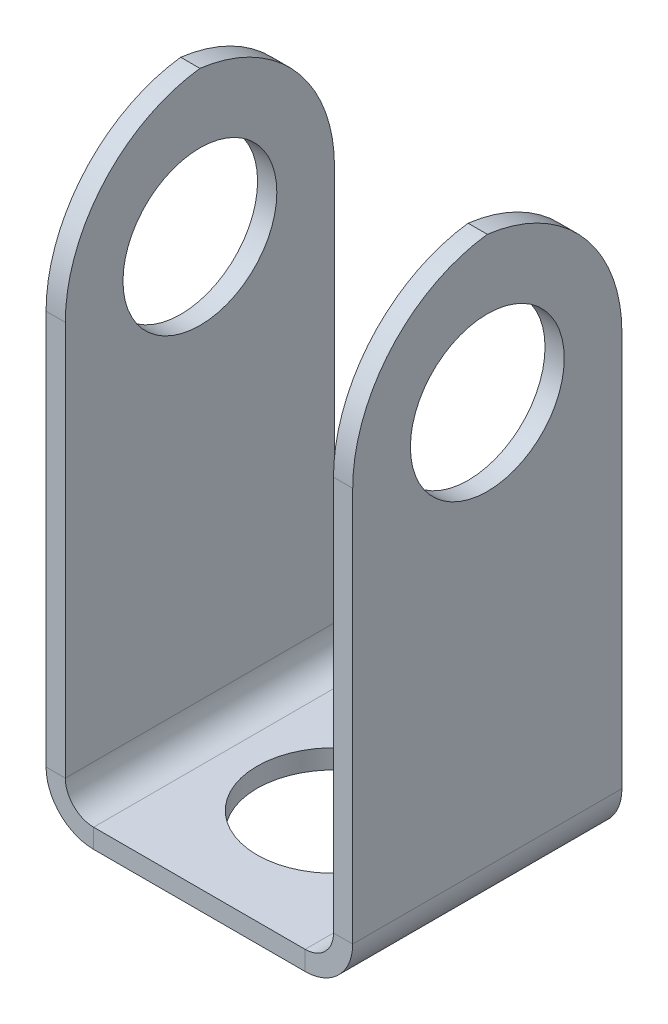
SolidWorks part; units mm, degrees
note: The reader was unsure of these and kept them because the rebuilt part matched: flange length of "Edge-Flange1", "Edge-Flange2".
ref_plane "Front Plane" through (0, 0, 0) normal (0, 0, 1) x (1, 0, 0)
ref_plane "Top Plane" through (0, 0, 0) normal (0, 1, 0) x (1, 0, 0)
ref_plane "Right Plane" through (0, 0, 0) normal (1, 0, 0) x (0, 0, -1)
sketch "Sketch1" plane through (0, 0, 0) normal (0, 1, 0) x (1, 0, 0)
  line L1 (-2.75, 3.5) -> (2.75, 3.5)
  line L2 (-2.75, 3.5) -> (-2.75, -3.5)
  line L3 (-2.75, -3.5) -> (2.75, -3.5)
  line L4 (2.75, 3.5) -> (2.75, -3.5)
  line L5 (-2.75, 3.5) -> (2.75, -3.5) construction
  line L6 (-2.75, -3.5) -> (2.75, 3.5) construction
  point P0 (0, 0)
base flange "Base-Flange1" sketch "Sketch1" thickness 0.5 reverse thickness direction yes parameters "D1"=0.7366
edge flange "Edge-Flange1" sketch "Sketch8" flange angle 90 flange length 15 flange position bend outside bend radius 0.7366 thickness 0.5 relief rectangular parameters "D6"=10
sketch "Sketch8" plane through (2.75, 0.5, 0) normal (1, 0, 0) x (0, 0, -1)
  line L0 (-3.5, 0) -> (3.5, 0) construction
  line L1 (-3.5, 0) -> (3.5, 0)
  line L2 (-3.5, 0) -> (-3.5, 15)
  line L3 (-3.5, 15) -> (3.5, 15)
  line L4 (3.5, 15) -> (3.5, 0)
bend "EdgeBend1" bend radius 0.7366 bend angle 90 parameters "D5"=1
edge flange "Edge-Flange2" sketch "Sketch11" flange angle 90 flange length 15 flange position bend outside bend radius 0.7366 thickness 0.5 relief rectangular parameters "D6"=10
sketch "Sketch11" plane through (-2.75, 0.5, 0) normal (-1, 0, 0) x (0, 0, 1)
  line L0 (-3.5, 0) -> (3.5, 0) construction
  line L1 (-3.5, 0) -> (3.5, 0)
  line L2 (-3.5, 0) -> (-3.5, 15)
  line L3 (-3.5, 15) -> (3.5, 15)
  line L4 (3.5, 15) -> (3.5, 0)
bend "EdgeBend2" bend radius 0.7366 bend angle 90 parameters "D5"=2
fillet "Fillet1" radius 4 4 edges at (3.7366, 15.5, -3.5) (-3.7366, 15.5, -3.5) (3.7366, 15.5, 3.5) (-3.7366, 15.5, 3.5)
sketch "Sketch12" plane through (0, 0.5, 0) normal (0, 1, 0) x (1, 0, 0)
  circle A0 centre (0, 0) radius 2
extrude "Cut-Extrude1" cut sketch "Sketch12" against normal through all normal cut yes
sketch "Sketch13" plane through (3.9866, 0, 0) normal (1, 0, 0) x (0, 0, -1)
  circle A0 centre (0, 11.6781) radius 2
extrude "Cut-Extrude2" cut sketch "Sketch13" against normal through all normal cut yes
sketch "Bend-Lines1" plane through (0, 0, 0) normal (0, 1, 0) x (1, 0, 0)
sketch "Bounding-Box1" plane through (0, 0, 0) normal (0, 1, 0) x (1, 0, 0)
sheet metal parameters "Sheet-Metal1" thickness 0.5 parameters "D1"=0.7366
flat pattern "Flat-Pattern1" [suppressed]
sketch "Bend-Lines2" plane through (0, 0, 0) normal (0, 1, 0) x (1, 0, 0)
sketch "Bounding-Box2" [suppressed] plane through (0, 0, 0) normal (0, 1, 0) x (1, 0, 0)
sheet metal parameters "Sheet-Metal2" thickness 0.5 parameters "D1"=0.7366
flat pattern "Flat-Pattern1" [suppressed]
sketch "Bend-Lines2" plane through (0, 0, 0) normal (0, 1, 0) x (1, 0, 0)
sketch "Bounding-Box2" [suppressed] plane through (0, 0, 0) normal (0, 1, 0) x (1, 0, 0)
bend of the flat pattern "Flatten-<EdgeBend1>1"
sheet metal parameters "Sheet-Metal3" thickness 0.5 parameters "D1"=0.7366
flat pattern "Flat-Pattern1" [suppressed]
sketch "Bend-Lines2" plane through (0, 0, 0) normal (0, 1, 0) x (1, 0, 0)
sketch "Bounding-Box2" [suppressed] plane through (0, 0, 0) normal (0, 1, 0) x (1, 0, 0)
bend of the flat pattern "Flatten-<EdgeBend1>1"
bend of the flat pattern "Flatten-<EdgeBend2>1"
sheet metal parameters "Sheet-Metal4" thickness 0.5 parameters "D1"=0.7366
flat pattern "Flat-Pattern1" [suppressed]
sketch "Bend-Lines2" plane through (0, 0, 0) normal (0, 1, 0) x (1, 0, 0)
sketch "Bounding-Box2" [suppressed] plane through (0, 0, 0) normal (0, 1, 0) x (1, 0, 0)
bend of the flat pattern "Flatten-<EdgeBend1>1"
bend of the flat pattern "Flatten-<EdgeBend2>1"
sheet metal parameters "Sheet-Metal5" thickness 0.5 parameters "D1"=0.7366
flat pattern "Flat-Pattern1" [suppressed]
sketch "Bend-Lines2" plane through (0, 0, 0) normal (0, 1, 0) x (1, 0, 0)
sketch "Bounding-Box2" [suppressed] plane through (0, 0, 0) normal (0, 1, 0) x (1, 0, 0)
bend of the flat pattern "Flatten-<EdgeBend1>1"
bend of the flat pattern "Flatten-<EdgeBend2>1"
